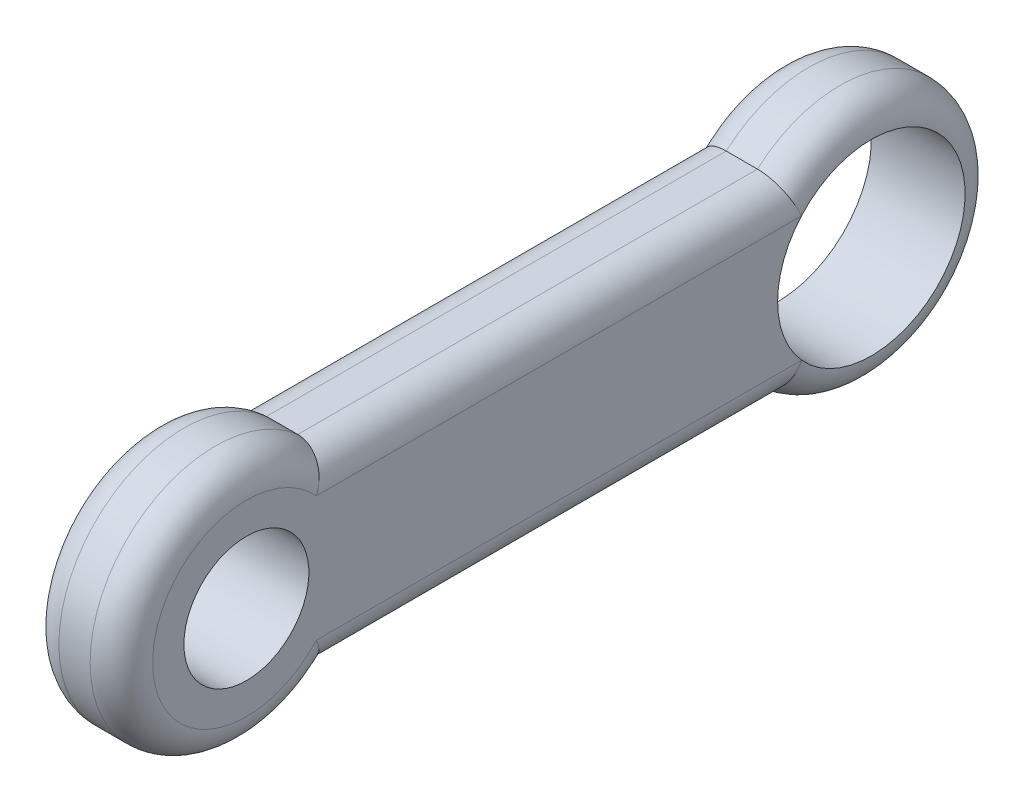
SolidWorks part; units mm, degrees
ref_plane "Front Plane" through (0, 0, 0) normal (0, 0, 1) x (1, 0, 0)
ref_plane "Top Plane" through (0, 0, 0) normal (0, 1, 0) x (1, 0, 0)
ref_plane "Right Plane" through (0, 0, 0) normal (1, 0, 0) x (0, 0, -1)
sketch "Sketch1" plane through (0, 0, 0) normal (1, 0, 0) x (0, 0, -1)
  line L0 (0, 0) -> (-20, 0) construction
  line L1 (55, 0) -> (-55, 0) construction
  line L2 (0, 0) -> (-20, 0) construction
  line L3 (-2.6458, -3) -> (-17.3542, -3)
  line L4 (-2.6458, 3) -> (-17.3542, 3)
  arc A2 (-17.3542, 3) -> (-17.3542, -3) centre (-20, 0) ccw
  arc A3 (-2.6458, -3) -> (-2.6458, 3) centre (0, 0) ccw
  point P5 (-10, 0)
extrude "Boss-Extrude1" add sketch "Sketch1" along normal blind 3
sketch "Sketch2" plane through (0, 0, 0) normal (1, 0, 0) x (0, 0, -1)
  circle A1 centre (0, 0) radius 3
  dimension "D1" = 6
extrude "Cut-Extrude1" cut sketch "Sketch2" along normal blind 3 contours A1
sketch "Sketch3" plane through (0, 0, 0) normal (-1, 0, 0) x (0, 0, 1)
  circle A0 centre (20, 0) radius 2
  dimension "D1" = 4
extrude "Cut-Extrude2" cut sketch "Sketch3" against normal blind 3
fillet "Fillet1" radius 1 8 edges at (0, 0, -4) (0, -3, 10) (0, 0, 24) (0, 3, 10) (3, 0, -4) (3, -3, 10) (3, 3, 10) (3, 0, 24)
scale "Scale1" scale about origin uniform scaling yes scale factor 1.5
